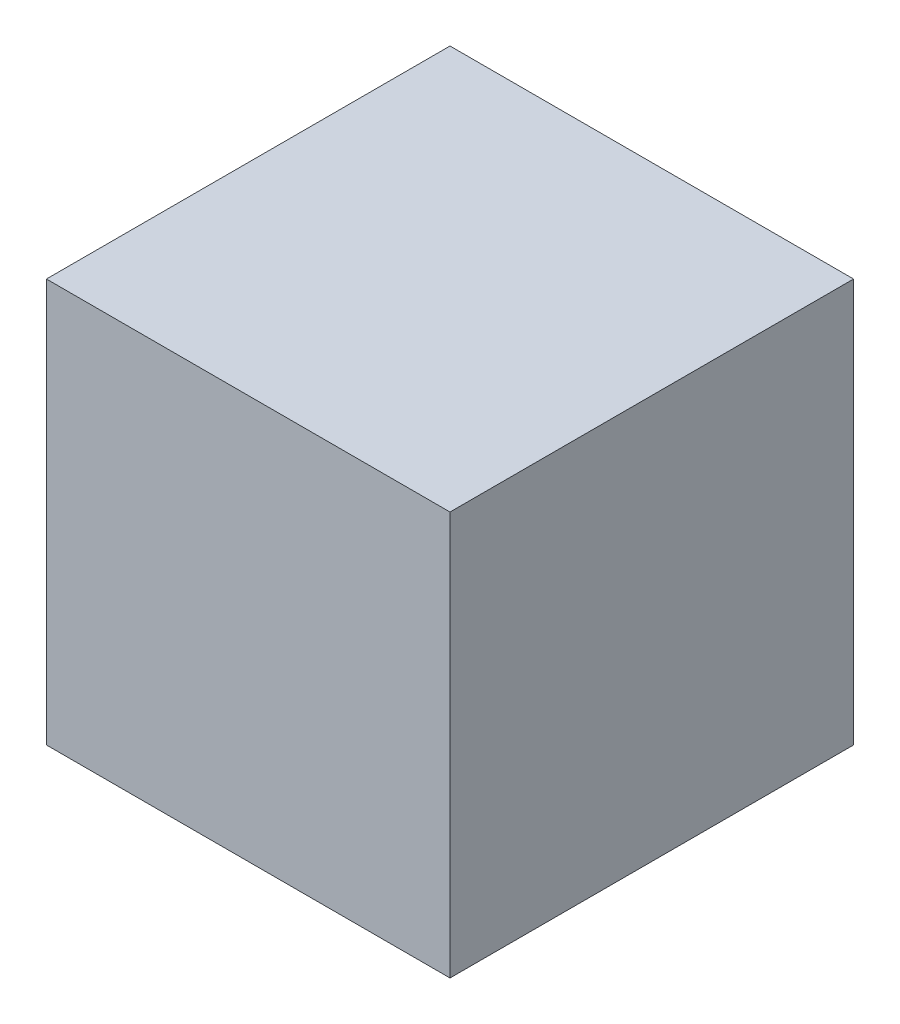
SolidWorks part; units mm, degrees
ref_plane "Front Plane" through (0, 0, 0) normal (0, 0, 1) x (1, 0, 0)
ref_plane "Top Plane" through (0, 0, 0) normal (0, 1, 0) x (1, 0, 0)
ref_plane "Right Plane" through (0, 0, 0) normal (1, 0, 0) x (0, 0, -1)
sketch "Sketch1" plane through (0, 0, 0) normal (1, 0, 0) x (0, 0, -1)
  line L1 (-80.01, -80.01) -> (80.01, -80.01)
  line L2 (-80.01, -80.01) -> (-80.01, 80.01)
  line L3 (-80.01, 80.01) -> (80.01, 80.01)
  line L4 (80.01, -80.01) -> (80.01, 80.01)
  line L5 (-80.01, -80.01) -> (80.01, 80.01) construction
  line L6 (-80.01, 80.01) -> (80.01, -80.01) construction
  point P0 (0, 0)
  dimension "Size" = 160.02
extrude "Boss-Extrude1" add sketch "Sketch1" along normal mid plane 160.02
equation "\"D1@Boss-Extrude1\" = \"Size@Sketch1\""
